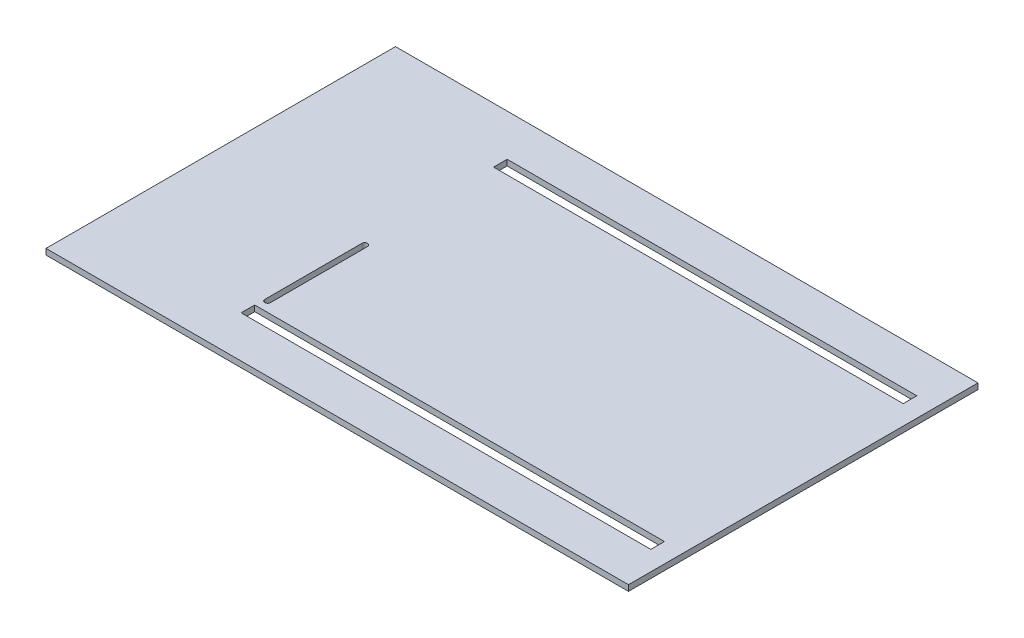
SolidWorks part; units mm, degrees
ref_plane "정면" through (0, 0, 0) normal (0, 0, 1) x (1, 0, 0)
ref_plane "윗면" through (0, 0, 0) normal (0, 1, 0) x (1, 0, 0)
ref_plane "우측면" through (0, 0, 0) normal (1, 0, 0) x (0, 0, -1)
sketch "스케치1" plane through (0, 0, 0) normal (0, 1, 0) x (1, 0, 0)
  line L1 (0, 0) -> (300, 0)
  line L2 (0, 0) -> (0, 180)
  line L3 (0, 180) -> (300, 180)
  line L4 (300, 0) -> (300, 180)
  dimension "D1" = 180
  dimension "D2" = 300
extrude "보스-돌출1" add sketch "스케치1" along normal blind 3
sketch "스케치2" plane through (0, 3, 0) normal (0, 1, 0) x (1, 0, 0)
  line L0 (93, 58.6066) -> (93.0904, 58.6066) construction
  line L1 (93, 56.1066) -> (93, 61.1066) construction
  line L3 (79.1, 58.6066) -> (79.1, 83.6066)
  line L4 (79.1, 33.6066) -> (82, 33.6066)
  line L5 (79.1, 33.6066) -> (79.1, 58.6066)
  line L6 (79.1, 83.6066) -> (82, 83.6066)
  line L7 (82, 33.6066) -> (82, 83.6066)
  line L8 (80.1, 78.7292) -> (80.1, 80.9866) construction
  line L10 (81, 78.7292) -> (81, 80.9866) construction
  dimension "D1" = 1
  dimension "D2" = 1
  dimension "D3" = 25
  dimension "D4" = 25
extrude "컷-돌출1" cut sketch "스케치2" against normal blind 10
sketch "스케치3" plane through (0, 3, 0) normal (0, 1, 0) x (1, 0, 0)
  line L0 (82, 83.6066) -> (79.1, 83.6066) construction
  line L1 (79.1, 33.6066) -> (82, 33.6066) construction
  circle A0 centre (80.55, 83.6066) radius 1.45
  circle A1 centre (80.55, 33.6066) radius 1.45
extrude "컷-돌출2" cut sketch "스케치3" against normal blind 10
sketch "스케치4" plane through (0, 3, 0) normal (0, 1, 0) x (1, 0, 0)
  line L0 (267.1496, 157.5) -> (284.01, 157.5) construction
  line L1 (290, 158.5) -> (79, 158.5)
  line L2 (290, 158.5) -> (290, 151.5)
  line L3 (290, 151.5) -> (79, 151.5)
  line L4 (79, 158.5) -> (79, 151.5)
  line L5 (79, 21.5) -> (290, 21.5)
  line L6 (79, 21.5) -> (79, 28.5)
  line L7 (79, 28.5) -> (290, 28.5)
  line L8 (290, 21.5) -> (290, 28.5)
  line L9 (267.1496, 152.5) -> (284.01, 152.5) construction
  line L10 (267.1496, 27.5) -> (284.01, 27.5) construction
  line L11 (300, 0) -> (300, 180) construction
  line L12 (0, 180) -> (0, 0) construction
  dimension "D1" = 1
  dimension "D2" = 1
  dimension "D3" = 1
  dimension "D4" = 10
  dimension "D5" = 79
extrude "컷-돌출3" cut sketch "스케치4" against normal blind 10
